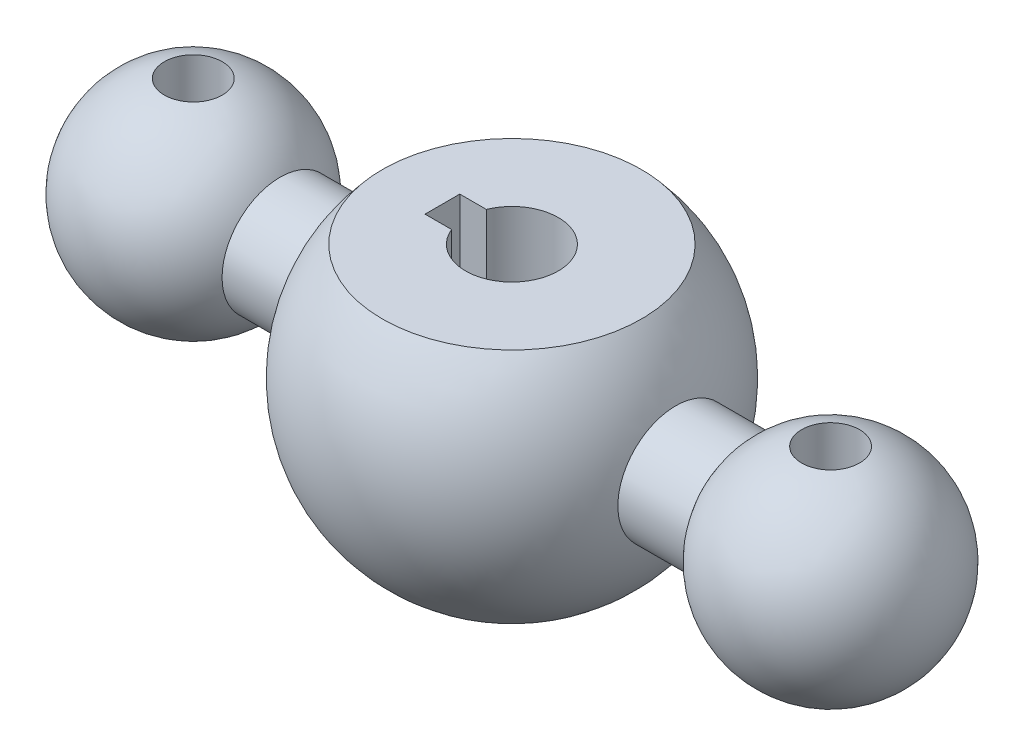
SolidWorks part; units mm, degrees
ref_plane "Front Plane" through (0, 0, 0) normal (0, 0, 1) x (1, 0, 0)
ref_plane "Top Plane" through (0, 0, 0) normal (0, 1, 0) x (1, 0, 0)
ref_plane "Right Plane" through (0, 0, 0) normal (1, 0, 0) x (0, 0, -1)
sketch "Sketch1" plane through (0, 0, 0) normal (0, 0, 1) x (1, 0, 0)
  line L0 (0, 49.2396) -> (0, 33.2987) construction
  line L1 (0, 10) -> (11.1803, 10)
  line L2 (9, -12) -> (0, -12)
  line L3 (0, 10) -> (0, -12)
  arc A0 (11.1803, 10) -> (9, -12) centre (0, 0) cw
  point P7 (41.5045, -57.7414)
  point P8 (41.2988, -58.8042)
  point P9 (43.7489, 10)
  point P11 (56.1473, -12)
  point P12 (0, 10)
  point P13 (10.2146, 10)
  point P14 (0, 0)
  dimension "D2" = 10
  dimension "D4" = 15
  dimension "D1" = 0
  dimension "D3" = 12
revolve "Revolve1" add sketch "Sketch1" angle 360 about L0
sketch "Sketch2" plane through (0, 0, 0) normal (0, 0, 1) x (1, 0, 0)
  line L0 (0, -7.2397) -> (0, -4.3438) construction
sketch "Sketch3" plane through (0, 10, 0) normal (0, 1, 0) x (1, 0, 0)
  line L0 (-6, 1.5) -> (-6, -1.5)
  line L1 (-6, -1.5) -> (-3.7081, -1.5)
  line L2 (-6, 1.5) -> (-3.7081, 1.5)
  line L3 (7.5727, 0) -> (4.7522, 0) construction
  line L4 (4.7522, 0) -> (5.7954, 0) construction
  arc A0 (-3.7081, 1.5) -> (-3.7081, -1.5) centre (0, 0) cw
  dimension "D1" = 4
  dimension "D2" = 3
  dimension "D3" = 6
extrude "Cut-Extrude1" cut sketch "Sketch3" against normal blind 25
sketch "Sketch4" plane through (0, 0, 0) normal (0, 1, 0) x (1, 0, 0)
  line L0 (-10.509, 0) -> (-2.4727, 0) construction
  line L1 (18.5, 0) -> (36.5, 0)
  line L2 (18.5, 0) -> (36.5, 0)
  arc A1 (18.5, 0) -> (36.5, 0) centre (27.5, 0) cw
  point P6 (36.5, 0)
  dimension "D1" = 9
  dimension "D2" = 27.5
revolve "Revolve2" add sketch "Sketch4" angle 360 about L0 region at (27.5, 0, -3.8197)
sketch "Sketch5" plane through (0, 0, 0) normal (0, 0, 1) x (1, 0, 0)
  line L0 (23.3769, -8) -> (31.6231, -8)
  circle A0 centre (27.5, 0) radius 9 construction
  arc A1 (23.3769, -8) -> (31.6231, -8) centre (27.5, 0) ccw
  point P5 (19.3847, -3.8913)
  point P7 (31.6231, -8)
  dimension "D2" = 9
  dimension "D1" = 8
extrude "Cut-Extrude2" cut sketch "Sketch5" against normal blind 25 and the other way blind 25
sketch "Sketch6" plane through (0, 0, 0) normal (0, 1, 0) x (1, 0, 0)
  circle A0 centre (27.5, 0) radius 2.5
  point P2 (0, 0)
  dimension "D1" = 5
  dimension "D2" = 27.5
extrude "Cut-Extrude3" cut sketch "Sketch6" against normal blind 25 and the other way blind 25
sketch "Sketch7" plane through (0, 0, 0) normal (0, 1, 0) x (1, 0, 0)
  line L0 (14.1421, 5) -> (20.0167, 5)
  line L1 (-19.8984, 0) -> (-9.1356, 0) construction
  line L2 (14.1421, 5) -> (14.1421, 0)
  line L3 (20.0167, 5) -> (20.0167, 0)
  line L4 (20.0167, 0) -> (14.1421, 0)
  circle A0 centre (0, 0) radius 15 construction
  circle A1 centre (27.5, 0) radius 9 construction
  dimension "D1" = 5
revolve "Revolve3" add sketch "Sketch7" angle 360 about L4
sketch "Sketch8" plane through (0, 0, 0) normal (0, 1, 0) x (1, 0, 0)
  line L0 (52.4121, 0) -> (47.8619, 0) construction
  line L1 (-36.5, 0) -> (-18.5, 0)
  arc A0 (-18.5, 0) -> (-36.5, 0) centre (-27.5, 0) ccw
  point P6 (-20.1958, 0)
  dimension "D2" = 9
  dimension "D1" = 27.5
revolve "Revolve4" add sketch "Sketch8" angle 360 about L0
sketch "Sketch9" plane through (0, 0, 0) normal (0, 0, 1) x (1, 0, 0)
  line L0 (-31.6231, -8) -> (-23.3769, -8)
  circle A0 centre (-27.5, 0) radius 9 construction
  arc A1 (-31.6231, -8) -> (-23.3769, -8) centre (-27.5, 0) ccw
  dimension "D1" = 9
  dimension "D2" = 8
extrude "Cut-Extrude4" cut sketch "Sketch9" against normal blind 25 and the other way blind 25 contours L0 A1
sketch "Sketch11" plane through (0, 0, 0) normal (0, 1, 0) x (1, 0, 0)
  circle A0 centre (-27.5, 0) radius 2.5
  dimension "D1" = 5
  dimension "D2" = 27.5
extrude "Cut-Extrude5" cut sketch "Sketch11" against normal blind 25 and the other way blind 25
sketch "Sketch12" plane through (0, 0, 0) normal (0, 1, 0) x (1, 0, 0)
  line L0 (-20.0167, 5) -> (-14.1421, 5)
  line L1 (-4.5636, 0) -> (-8.5929, 0) construction
  line L2 (-20.0167, 5) -> (-20.0167, 0)
  line L3 (-20.0167, 0) -> (-14.1421, 0)
  line L4 (-14.1421, 0) -> (-14.1421, 5)
  circle A0 centre (-27.5, 0) radius 9 construction
  arc A1 (14.1421, 5) -> (14.1421, -5) centre (0, 0) ccw construction
  dimension "D1" = 5
revolve "Revolve5" add sketch "Sketch12" angle 360 about L1
